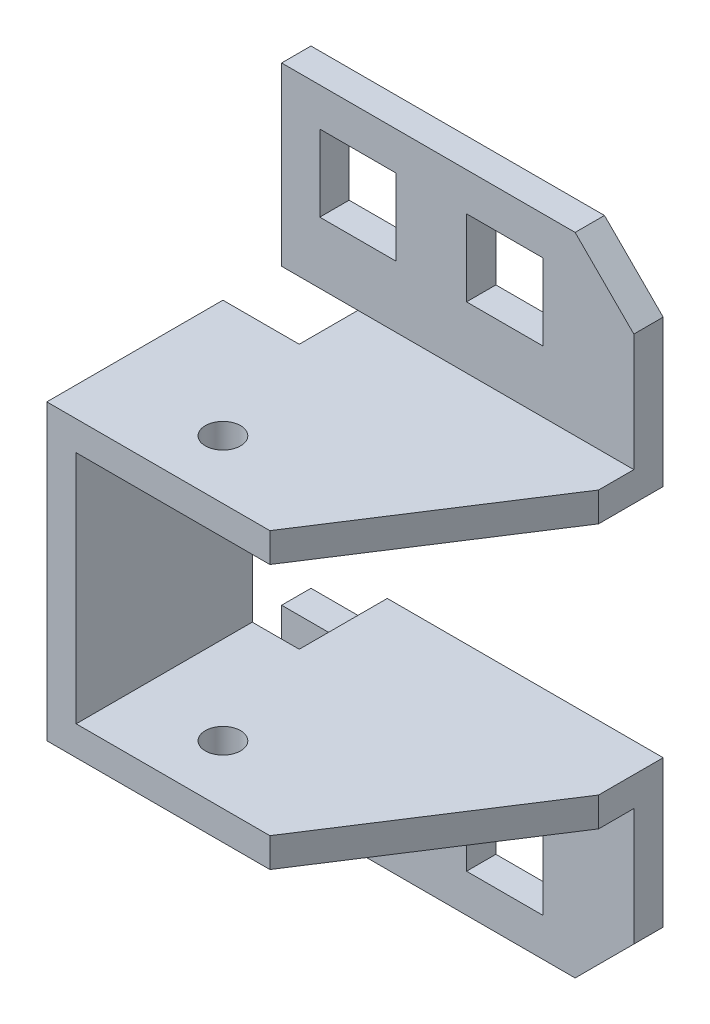
SolidWorks part; units mm, degrees
ref_plane "Front Plane" through (0, 0, 0) normal (0, 0, 1) x (1, 0, 0)
ref_plane "Top Plane" through (0, 0, 0) normal (0, 1, 0) x (1, 0, 0)
ref_plane "Right Plane" through (0, 0, 0) normal (1, 0, 0) x (0, 0, -1)
sketch "Sketch1" plane through (0, 0, 0) normal (0, 0, 1) x (1, 0, 0)
  line L0 (0, 0) -> (50, 0)
  line L1 (50, 0) -> (60, 10)
  line L2 (60, 10) -> (60, 30)
  line L12 (60, 30) -> (0, 30)
  line L13 (0, 30) -> (0, 0)
  line L14 (0, 55) -> (60, 55) construction
  line L15 (0, 80) -> (0, 110)
  line L16 (60, 80) -> (0, 80)
  line L17 (60, 100) -> (60, 80)
  line L18 (50, 110) -> (60, 100)
  line L19 (0, 110) -> (50, 110)
  dimension "D1" = 60
  dimension "D2" = 25
  dimension "D3" = 50
  dimension "D4" = 20
  dimension "D5" = 30
extrude "Boss-Extrude4" add sketch "Sketch1" along normal blind 5
sketch "Sketch3" plane through (0, 0, 5) normal (0, 0, 1) x (1, 0, 0)
  line L0 (50, 110) -> (0, 110) construction
  line L1 (6.5, 103.5) -> (19.5, 103.5)
  line L2 (6.5, 103.5) -> (6.5, 90.5)
  line L3 (6.5, 90.5) -> (19.5, 90.5)
  line L4 (19.5, 103.5) -> (19.5, 90.5)
  line L5 (31.5, 103.5) -> (44.5, 103.5)
  line L6 (31.5, 103.5) -> (31.5, 90.5)
  line L7 (31.5, 90.5) -> (44.5, 90.5)
  line L8 (44.5, 103.5) -> (44.5, 90.5)
  line L9 (6.5, 19.5) -> (19.5, 19.5)
  line L10 (6.5, 19.5) -> (6.5, 6.5)
  line L11 (6.5, 6.5) -> (19.5, 6.5)
  line L12 (19.5, 19.5) -> (19.5, 6.5)
  line L13 (31.5, 19.5) -> (44.5, 19.5)
  line L14 (31.5, 19.5) -> (31.5, 6.5)
  line L15 (31.5, 6.5) -> (44.5, 6.5)
  line L16 (44.5, 19.5) -> (44.5, 6.5)
  line L17 (0, 110) -> (0, 80) construction
  line L18 (0, 0) -> (50, 0) construction
  point P16 (6.5, 97)
  point P19 (13, 103.5)
  point P22 (38, 103.5)
  point P23 (6.5, 13)
  dimension "D1" = 13
  dimension "D2" = 13
  dimension "D3" = 13
  dimension "D4" = 38
  dimension "D5" = 13
extrude "Cut-Extrude2" cut sketch "Sketch3" against normal through all
sketch "Sketch4" plane through (0, 30, 0) normal (0, 1, 0) x (1, 0, 0)
  line L0 (60, -5) -> (60, -11)
  line L1 (60, -11) -> (38, -45)
  line L2 (38, -45) -> (0, -45)
  line L3 (0, -45) -> (0, -15)
  line L4 (0, -15) -> (13, -15)
  line L5 (13, -15) -> (13, -5)
  line L6 (50, -5) -> (0, -5) construction
  line L8 (60, -5) -> (60, 0)
  line L9 (60, 0) -> (13, 0)
  line L10 (50, 0) -> (0, 0) construction
  line L11 (31.5, -5) -> (44.5, -5) construction
  line L12 (13, 0) -> (13, -5)
  point P16 (38, -5)
  dimension "D1" = 10
  dimension "D2" = 6
  dimension "D3" = 30
  dimension "D4" = 13
extrude "Boss-Extrude5" add sketch "Sketch4" along normal blind 5
extrude "Boss-Extrude6" add sketch "Sketch4<2>" against normal blind 5 from surface starting at face at (30, 80, 2.5)
sketch "Sketch4<2>" plane through (0, 30, 0) normal (0, 1, 0) x (1, 0, 0) same geometry as "Sketch4"
sketch "Sketch5" plane through (0, 35, 0) normal (0, 1, 0) x (1, 0, 0)
  line L0 (38, -45) -> (0, -45) construction
  line L1 (0, -15) -> (5, -15)
  line L2 (0, -15) -> (0, -45)
  line L3 (0, -45) -> (5, -45)
  line L4 (5, -15) -> (5, -45)
  dimension "D1" = 5
extrude "Boss-Extrude7" add sketch "Sketch5" along normal up to surface (40 mm away) up to face at (26.2857, 75, 18.7143)
sketch "Sketch6" plane through (0, 80, 0) normal (0, 1, 0) x (1, 0, 0)
  line L0 (0, -45) -> (0, -15) construction
  line L1 (38, -45) -> (0, -45) construction
  circle A0 centre (20, -35) radius 3
  dimension "D1" = 6
  dimension "D2" = 20
  dimension "D3" = 10
extrude "Cut-Extrude3" cut sketch "Sketch6" against normal through all
